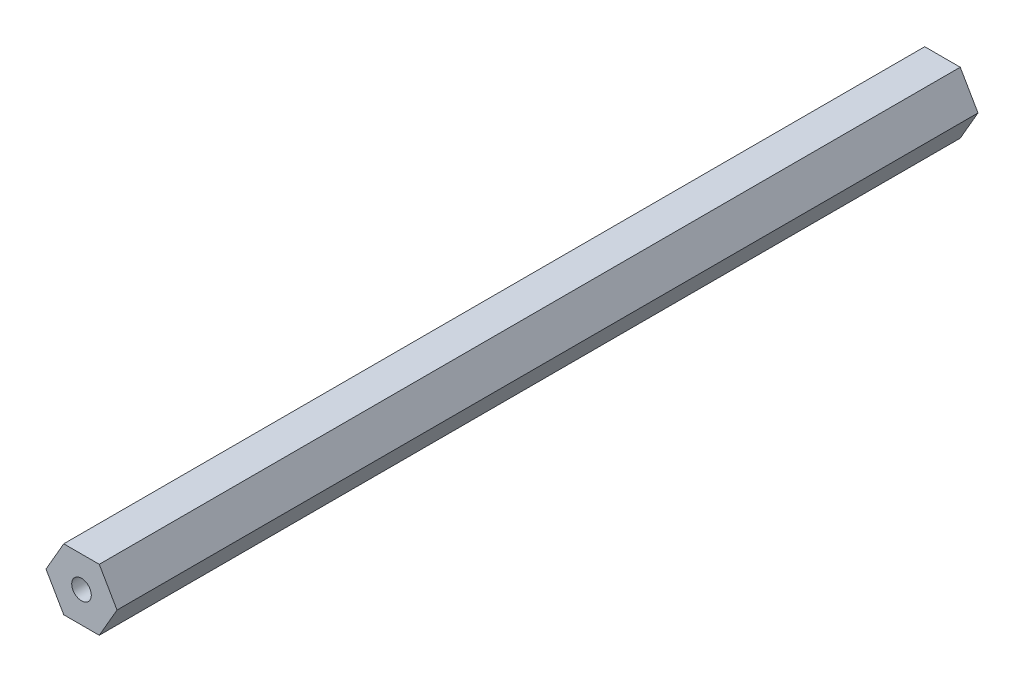
SolidWorks part; units mm, degrees
material "6061-T6 (SS)"
ref_plane "Front" through (0, 0, 0) normal (0, 0, 1) x (1, 0, 0)
ref_plane "Top" through (0, 0, 0) normal (0, 1, 0) x (1, 0, 0)
ref_plane "Right" through (0, 0, 0) normal (1, 0, 0) x (0, 0, -1)
sketch "Sketch1" plane through (0, 0, 0) normal (0, 0, 1) x (1, 0, 0)
  line L1 (7.3323, 0) -> (3.6662, 6.35)
  line L2 (3.6662, 6.35) -> (-3.6662, 6.35)
  line L3 (-3.6662, 6.35) -> (-7.3323, 0)
  line L4 (-7.3323, 0) -> (-3.6662, -6.35)
  line L5 (-3.6662, -6.35) -> (3.6662, -6.35)
  line L6 (3.6662, -6.35) -> (7.3323, 0)
  circle A0 centre (0, 0) radius 6.35 construction
  dimension "D1" = 12.7
extrude "Boss-Extrude1" add sketch "Sketch1" along normal blind 177.8
hole_wizard "#10-32 Tapped Hole1" positions "Sketch2" profile "Sketch4" tap size "#10-32" standard "ANSI Inch"
sketch "Sketch2" plane through (0, 0, 177.8) normal (0, 0, 1) x (1, 0, 0)
  point P0 (0, 0)
sketch "Sketch4" plane through (0, 0, 177.8) normal (1, 0, 0) x (0, -1, 0)
  line L0 (0, 0) -> (0, 77.4133)
  line L1 (0, 77.4133) -> (2.0193, 76.2)
  line L2 (2.0193, 76.2) -> (2.0193, 0)
  line L5 (2.0193, 0) -> (0, 0)
  line L10 (0, 77.4133) -> (-2.0193, 76.2) construction
  line L11 (0, -6.35) -> (0, 107.95) construction
  dimension "Tap Drill Dia." = 4.0386
  dimension "Tap Drill Depth" = 76.2
  dimension "Drill Angle" = 118
cosmetic thread "Hole Thread1" parameters "D1"=9.652, "D2"=4.826
